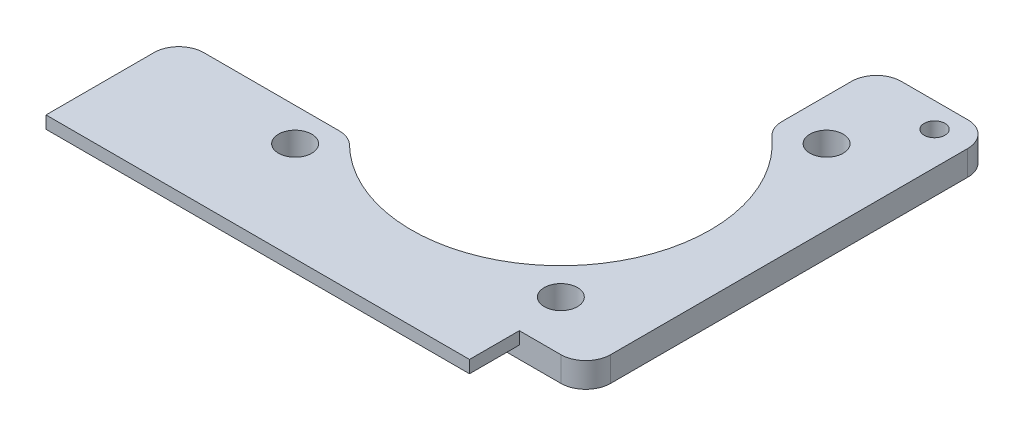
SolidWorks part; units mm, degrees
ref_plane "Front Plane" through (0, 0, 0) normal (0, 0, 1) x (1, 0, 0)
ref_plane "Top Plane" through (0, 0, 0) normal (0, 1, 0) x (1, 0, 0)
ref_plane "Right Plane" through (0, 0, 0) normal (1, 0, 0) x (0, 0, -1)
sketch "Sketch1" plane through (0, 0, 0) normal (0, 1, 0) x (1, 0, 0)
  line L1 (0, 0) -> (51, 0)
  line L2 (0, 0) -> (0, -6)
  line L3 (0, -6) -> (51, -6)
  line L4 (51, 0) -> (51, -6)
  dimension "D1" = 51
  dimension "D2" = 6
extrude "Boss-Extrude1" add sketch "Sketch1" against normal blind 1.5
sketch "Sketch3" plane through (0, 0, 0) normal (0, 1, 0) x (1, 0, 0)
  line L1 (59, 0) -> (59, 49)
  line L2 (59, 49) -> (45, 49)
  line L3 (45, 49) -> (45, 36.2478)
  line L5 (20.5836, 10) -> (0, 10)
  line L6 (0, 10) -> (0, 0)
  line L8 (59, 0) -> (0, 0)
  line L10 (-4, 4) -> (59, 4) construction
  line L11 (18, 6) -> (50, 38) construction
  line L12 (52, 49) -> (52, 0) construction
  line L13 (34, 22) -> (34, 4) construction
  line L14 (51, -6) -> (51, 0) construction
  line L15 (18, 6) -> (50, 6) construction
  line L16 (18, 6) -> (18, 38) construction
  line L17 (18, 38) -> (50, 38) construction
  line L18 (50, 6) -> (50, 38) construction
  arc A0 (20.5836, 10) -> (45, 36.2478) centre (34, 22) ccw
  circle A1 centre (18, 6) radius 2
  circle A2 centre (50, 38) radius 2
  circle A3 centre (50, 6) radius 2
  circle A4 centre (55, 46) radius 1.25
  point P0 (0, 0)
  point P22 (34, 22)
  dimension "D4" = 18
  dimension "D5" = 45
  dimension "D7" = 4
  dimension "D8" = 4
  dimension "D10" = 4
  dimension "D13" = 2.5
  dimension "D1" = 10
  dimension "D2" = 14
  dimension "D3" = 49
  dimension "D6" = 32
  dimension "D9" = 7
  dimension "D11" = 4
  dimension "D12" = 4
  dimension "D14" = 8
  dimension "D15" = 46
extrude "Boss-Extrude2" add sketch "Sketch3" against normal blind 3
fillet "Fillet1" radius 3 6 edges at (59, -1.5, -49) (45, -1.5, -49) (0, -1.5, -10) (20.5836, -1.5, -10) (45, -1.5, -36.2478) (59, -1.5, 0)
